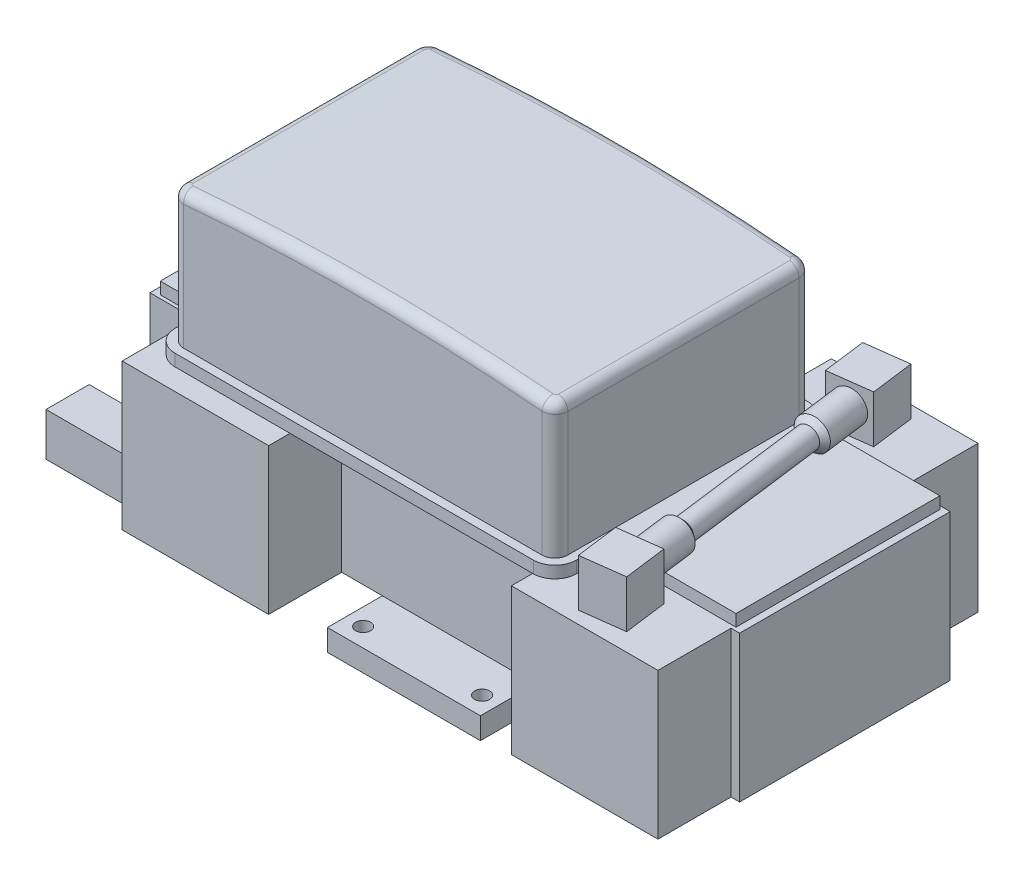
SolidWorks part; units mm, degrees
material "ASTM A36 Steel"
ref_plane "Front Plane" through (0, 0, 0) normal (0, 0, 1) x (1, 0, 0)
ref_plane "Top Plane" through (0, 0, 0) normal (0, 1, 0) x (1, 0, 0)
ref_plane "Right Plane" through (0, 0, 0) normal (1, 0, 0) x (0, 0, -1)
sketch "Sketch1" plane through (0, 0, 0) normal (1, 0, 0) x (0, 0, -1)
  line L0 (-43.0022, 0) -> (43.0022, 0)
  line L1 (43.0022, 0) -> (43.0022, 6.35)
  line L2 (43.0022, 6.35) -> (25.4, 6.35)
  line L3 (25.4, 6.35) -> (25.4, 10.4902)
  line L4 (25.4, 10.4902) -> (-25.4, 10.4902)
  line L5 (0, -13.2437) -> (0, -40.5462) construction
  line L6 (-25.4, 6.35) -> (-25.4, 10.4902)
  line L7 (-43.0022, 6.35) -> (-25.4, 6.35)
  line L8 (-43.0022, 0) -> (-43.0022, 6.35)
  dimension "D1" = 86.0044
  dimension "D2" = 6.35
  dimension "D3" = 10.4902
  dimension "D4" = 50.8
extrude "Boss-Extrude1" add sketch "Sketch1" along normal mid plane 45.0088
sketch "Sketch2" plane through (0, 10.4902, 0) normal (0, 1, 0) x (1, 0, 0)
  line L0 (41.0972, -52.4764) -> (84.2264, -52.4764)
  line L1 (84.2264, -52.4764) -> (84.2264, -30.988)
  line L2 (84.2264, -30.988) -> (86.7664, -30.988)
  line L3 (86.7664, -30.988) -> (86.7664, 30.988)
  line L4 (86.7664, 30.988) -> (73.4568, 30.988)
  line L5 (73.4568, 30.988) -> (73.4568, 52.4764)
  line L6 (73.4568, 52.4764) -> (30.3276, 52.4764)
  line L7 (30.3276, 52.4764) -> (30.3276, 30.988)
  line L8 (30.3276, 30.988) -> (-41.0972, 30.988)
  line L9 (-41.0972, 30.988) -> (-41.0972, 52.4764)
  line L10 (-41.0972, 52.4764) -> (-84.2264, 52.4764)
  line L11 (-84.2264, 52.4764) -> (-84.2264, 30.988)
  line L12 (-84.2264, 30.988) -> (-86.7664, 30.988)
  line L13 (-86.7664, 30.988) -> (-86.7664, -30.988)
  line L14 (-86.7664, -30.988) -> (-73.4568, -30.988)
  line L15 (-73.4568, -30.988) -> (-73.4568, -52.4764)
  line L16 (-73.4568, -52.4764) -> (-30.3276, -52.4764)
  line L17 (-30.3276, -52.4764) -> (-30.3276, -30.988)
  line L18 (-30.3276, -30.988) -> (41.0972, -30.988)
  line L19 (41.0972, -30.988) -> (41.0972, -52.4764)
  line L20 (73.4568, 30.988) -> (30.3276, 52.4764) construction
  line L21 (84.2264, -30.988) -> (41.0972, -52.4764) construction
  point P2 (86.7664, 0)
  point P21 (51.8922, 41.7322)
  point P23 (62.6618, -41.7322)
  dimension "D1" = 61.976
  dimension "D2" = 21.4884
  dimension "D3" = 21.4884
  dimension "D4" = 43.1292
  dimension "D5" = 13.3096
  dimension "D6" = 71.4248
  dimension "D7" = 173.5328
  dimension "D8" = 2.54
  dimension "D9" = 86.7664
  dimension "D10" = 13.3096
extrude "Boss-Extrude2" add sketch "Sketch2" along normal blind 43.0276
sketch "Sketch4" plane through (0, 53.5178, 0) normal (0, 1, 0) x (1, 0, 0)
  line L0 (-64.135, 34.5694) -> (41.275, 34.5694)
  line L2 (47.371, 29.9974) -> (84.709, 29.9974)
  line L3 (84.709, 29.9974) -> (84.709, -29.9974)
  line L4 (84.709, -29.9974) -> (47.625, -29.9974)
  line L5 (47.625, -29.9974) -> (47.625, -39.8526)
  line L6 (41.275, -46.2026) -> (-64.135, -46.2026)
  line L7 (-70.485, -39.8526) -> (-70.485, -29.9974)
  line L8 (-70.485, -29.9974) -> (-84.709, -29.9974)
  line L9 (-84.709, -29.9974) -> (-84.709, 29.9974)
  line L10 (-84.709, 29.9974) -> (-70.231, 29.9974)
  arc A0 (47.625, -39.8526) -> (41.275, -46.2026) centre (41.275, -39.8526) cw
  arc A1 (-64.135, -46.2026) -> (-70.485, -39.8526) centre (-64.135, -39.8526) cw
  arc A2 (-64.135, 34.5694) -> (-70.231, 29.9974) centre (-64.135, 28.2194) ccw
  arc A3 (41.275, 34.5694) -> (47.371, 29.9974) centre (41.275, 28.2194) cw
  point P2 (84.709, 0)
  dimension "D8" = 6.35
  dimension "D1" = 59.9948
  dimension "D2" = 80.772
  dimension "D3" = 118.11
  dimension "D4" = 14.224
  dimension "D5" = 4.572
  dimension "D6" = 169.418
  dimension "D7" = 84.709
extrude "Boss-Extrude3" add sketch "Sketch4" along normal blind 3.5052
sketch "Sketch5" plane through (0, 57.023, 0) normal (0, 1, 0) x (1, 0, 0)
  line L0 (-70.485, -39.8526) -> (-70.485, -29.9974) construction
  line L1 (-64.135, 32.0294) -> (41.275, 32.0294)
  line L2 (-67.945, 28.2194) -> (-67.945, -39.8526)
  line L3 (-64.135, -43.6626) -> (41.275, -43.6626)
  line L4 (45.085, 28.2194) -> (45.085, -39.8526)
  line L5 (41.275, -46.2026) -> (-64.135, -46.2026) construction
  line L6 (-64.135, 34.5694) -> (41.275, 34.5694) construction
  arc A0 (-67.945, -39.8526) -> (-64.135, -43.6626) centre (-64.135, -39.8526) ccw
  arc A1 (-64.135, 32.0294) -> (-67.945, 28.2194) centre (-64.135, 28.2194) ccw
  arc A2 (41.275, 32.0294) -> (45.085, 28.2194) centre (41.275, 28.2194) cw
  arc A3 (41.275, -43.6626) -> (45.085, -39.8526) centre (41.275, -39.8526) ccw
  point P18 (-11.43, -43.6626)
  dimension "D6" = 3.81
  dimension "D1" = 75.692
  dimension "D2" = 113.03
  dimension "D3" = 2.54
  dimension "D4" = 2.54
  dimension "D5" = 2.54
extrude "Boss-Extrude4" add sketch "Sketch5" along normal blind 50.8
sketch "Sketch6" plane through (0, 0, 0) normal (0, 0, 1) x (1, 0, 0)
  line L0 (-137.5167, 85.8525) -> (-137.5167, 170.8238)
  line L1 (-137.5167, 170.8238) -> (114.6567, 170.8238)
  line L2 (114.6567, 170.8238) -> (114.6567, 85.8525)
  arc A0 (114.6567, 85.8525) -> (-137.5167, 85.8525) centre (-11.43, -510.5654) ccw
  dimension "D1" = 609.6
  dimension "D2" = 42.0116
extrude "Cut-Extrude1" cut sketch "Sketch6" against normal mid plane 101.6
fillet "Fillet1" radius 3.048 8 edges at (44.2562, 96.4858, 42.2251) (45.085, 96.4092, 5.8166) (43.6622, 96.54, -31.1888) (-11.43, 99.0346, -32.0294) (-67.1162, 96.4858, -30.5919) (-67.945, 96.4092, 5.8166) (-66.5222, 96.54, 42.822) (-11.43, 99.0346, 43.6626)
sketch "Sketch7" plane through (-67.945, 0, 0) normal (-1, 0, 0) x (0, 0, 1)
  line L0 (-5.2202, 75.6666) -> (13.8054, 75.6666)
  line L1 (16.3068, 72.6855) -> (15.8052, 69.8407)
  line L2 (13.3038, 67.7418) -> (-4.7186, 67.7418)
  line L3 (-7.22, 69.8407) -> (-7.7216, 72.6855)
  line L4 (-28.2194, 57.023) -> (39.8526, 57.023) construction
  arc A0 (15.8052, 69.8407) -> (13.3038, 67.7418) centre (13.3038, 70.2818) cw
  arc A1 (-4.7186, 67.7418) -> (-7.22, 69.8407) centre (-4.7186, 70.2818) cw
  arc A2 (-5.2202, 75.6666) -> (-7.7216, 72.6855) centre (-5.2202, 73.1266) ccw
  arc A3 (13.8054, 75.6666) -> (16.3068, 72.6855) centre (13.8054, 73.1266) cw
  point P14 (4.2926, 75.6666)
  dimension "D3" = 2.54
  dimension "D1" = 10.7188
  dimension "D2" = 7.9248
  dimension "D4" = 80
  dimension "D5" = 80
  dimension "D6" = 39.37
  dimension "D7" = 24.0284
extrude "Boss-Extrude5" add sketch "Sketch7" along normal blind 6.5024
ref_plane "Plane1" through (0, 22.5, 0) normal (0, 1, 0) x (-1, 0, 0)
sketch "Sketch8" plane through (0, 22.5, 0) normal (0, 1, 0) x (-1, 0, 0)
  line L0 (89.0242, -45) -> (105.3472, -45) construction
  line L1 (96.9814, 38.65) -> (71.5814, 38.65)
  line L2 (96.9814, 38.65) -> (96.9814, 51.35)
  line L3 (96.9814, 51.35) -> (71.5814, 51.35)
  line L4 (71.5814, 38.65) -> (71.5814, 51.35)
  line L5 (105.3472, -51.35) -> (79.9472, -51.35)
  line L6 (105.3472, -51.35) -> (105.3472, -38.65)
  line L7 (105.3472, -38.65) -> (79.9472, -38.65)
  line L8 (79.9472, -51.35) -> (79.9472, -38.65)
  line L9 (81.0807, 45) -> (96.9814, 45) construction
  line L10 (41.0972, -52.4764) -> (84.2264, -52.4764) construction
  dimension "D1" = 25.4
  dimension "D2" = 12.7
  dimension "D3" = 45
  dimension "D4" = 7.4764
  dimension "D5" = 45
extrude "Boss-Extrude6" add sketch "Sketch8" along normal mid plane 12.7
sketch "Sketch9" plane through (0, 22.5, 0) normal (0, 1, 0) x (-1, 0, 0)
  line L0 (89.0242, -45) -> (105.3472, -45) construction
  line L1 (81.0807, 45) -> (96.9814, 45) construction
  circle A0 centre (97.8856, -45) radius 5.588
  circle A1 centre (88.635, 45) radius 5.588
  dimension "D1" = 11.176
extrude "Boss-Extrude7" [suppressed] add sketch "Sketch9" along normal blind 25.4
sketch "Sketch10" plane through (0, 0, 0) normal (0, 1, 0) x (1, 0, 0)
  circle A0 centre (17.5, -37.5) radius 2.2
  circle A1 centre (-17.5006, -37.5) radius 2.2
  circle A2 centre (-17.5006, 37.4904) radius 2.2
  circle A3 centre (17.5, 37.4904) radius 2.2
  dimension "D1" = 4.4
  dimension "D5" = 17.5006
  dimension "D2" = 37.5
  dimension "D3" = 37.4904
  dimension "D4" = 17.5
extrude "Cut-Extrude3" cut sketch "Sketch10" along normal blind 7.62
ref_plane "Plane2" through (56.339, 0, -7.2695) normal (-0.9918, 0, 0.128) x (0.128, 0, 0.9918)
sketch "Sketch11" plane through (56.339, 0, -7.2695) normal (-0.9918, 0, 0.128) x (0.128, 0, 0.9918)
  line L0 (49.408, 10.4902) -> (-34.7484, 10.4902) construction
  line L1 (43.058, 67.4994) -> (55.758, 67.4994)
  line L2 (43.058, 67.4994) -> (43.058, 51.7168)
  line L3 (43.058, 51.7168) -> (55.758, 51.7168)
  line L4 (55.758, 67.4994) -> (55.758, 51.7168)
  line L5 (7.3298, 10.4902) -> (7.3298, 29.8781) construction
  line L6 (-41.0984, 67.4994) -> (-41.0984, 51.7168)
  line L7 (-28.3984, 51.7168) -> (-41.0984, 51.7168)
  line L8 (-28.3984, 67.4994) -> (-28.3984, 51.7168)
  line L9 (-28.3984, 67.4994) -> (-41.0984, 67.4994)
  point P10 (49.408, 51.7168)
  dimension "D1" = 12.7
extrude "Boss-Extrude8" add sketch "Sketch11" along normal mid plane 12.7
sketch "Sketch12" plane through (56.339, 0, -7.2695) normal (-0.9918, 0, 0.128) x (0.128, 0, 0.9918)
  line L0 (43.058, 61.1494) -> (-28.3984, 61.1494)
  line L1 (43.058, 67.4994) -> (43.058, 51.7168) construction
  line L2 (-28.3984, 67.4994) -> (-28.3984, 51.7168) construction
  line L3 (43.058, 61.1494) -> (43.058, 65.9119)
  line L4 (43.058, 65.9119) -> (30.358, 65.9119)
  line L5 (30.358, 65.9119) -> (28.7705, 64.3244)
  line L6 (28.7705, 64.3244) -> (-14.1109, 64.3244)
  line L7 (-14.1109, 64.3244) -> (-15.6984, 65.9119)
  line L8 (-15.6984, 65.9119) -> (-28.3984, 65.9119)
  line L9 (-28.3984, 61.1494) -> (-28.3984, 65.9119)
  line L10 (43.058, 61.1494) -> (63.5993, 61.1494) construction
  line L11 (43.058, 67.4994) -> (55.758, 67.4994) construction
  dimension "D1" = 9.525
  dimension "D2" = 6.35
  dimension "D3" = 45
  dimension "D4" = 6.35
  dimension "D5" = 12.7
revolve "Revolve1" add sketch "Sketch12" angle 360 about L10
sketch "Sketch13" plane through (-67.945, 0, 0) normal (-1, 0, 0) x (0, 0, 1)
  circle A0 centre (23.9965, 79.5246) radius 3
  dimension "D1" = 6
extrude "Boss-Extrude9" add sketch "Sketch13" along normal blind 2.54
